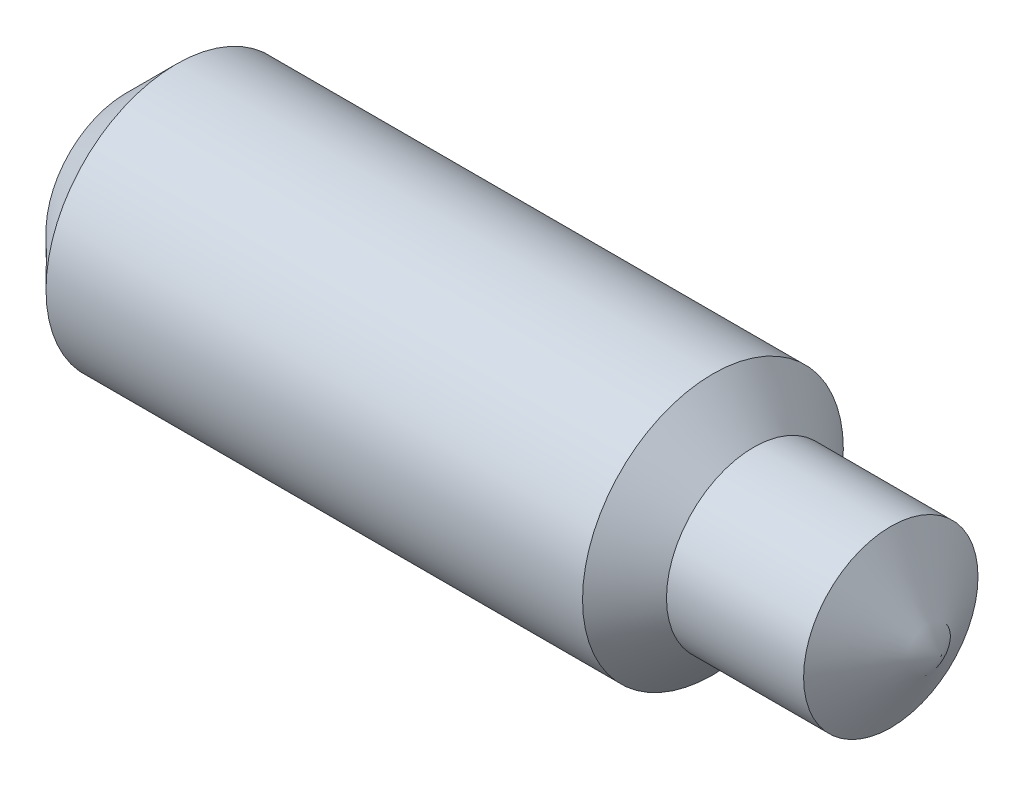
SolidWorks part; units mm, degrees
ref_plane "Front" through (0, 0, 0) normal (0, 0, 1) x (1, 0, 0)
ref_plane "Top" through (0, 0, 0) normal (0, 1, 0) x (1, 0, 0)
ref_plane "Right" through (0, 0, 0) normal (1, 0, 0) x (0, 0, -1)
sketch "Sketch1" plane through (0, 0, 0) normal (0, 0, 1) x (1, 0, 0)
  line L0 (-1.3284, 0) -> (23.5063, 0) construction
  line L1 (0, 0) -> (0, 4)
  line L2 (0, 4) -> (18, 4)
  line L3 (18, 4) -> (19.25, 2.675)
  line L4 (19.25, 2.675) -> (25, 2.675)
  line L5 (25, 0) -> (25, 2.675)
  line L6 (0, 0) -> (25, 0)
revolve "Base" add sketch "Sketch1" angle 360 about L0
cosmetic thread "ThreadCosmetic1" [suppressed] parameters "D1"=18, "D2"=4.917
chamfer "HeadChamfer" distance 1.5415 angle 45 1 edges at (0, 0, 4)
sketch "Sketch2" plane through (0, 0, 0) normal (0, 1, 0) x (1, 0, 0)
  line L0 (27.0527, 0) -> (22.5603, 0) construction
  line L2 (25, 0) -> (23.4556, 2.675)
  line L3 (25, -2.675) -> (25, 2.675) construction
  line L4 (23.4556, 2.675) -> (23.4556, 5)
  line L5 (0, 2.4585) -> (0, -2.4585) construction
  line L6 (-1.3284, 0) -> (23.5063, 0) construction
  line L8 (25, 2.675) -> (19.25, 2.675) construction
  line L9 (23.4556, 5) -> (27, 5)
  line L10 (27, 5) -> (27, 0)
  line L11 (27, 0) -> (25, 0)
  dimension "D1" = 60
  dimension "D3" = 10
  dimension "D2" = 27
revolve "Cut-Extrude3" cut sketch "Sketch2" angle 360 about L0
chamfer "Chamfer2" [suppressed] distance 1.5415 angle 45
sketch "Sketch3" plane through (0, 0, 0) normal (0, 0, 1) x (1, 0, 0)
  line L0 (0.7708, 4) -> (1.5415, 2.665)
  line L1 (1.5415, 2.665) -> (2.3123, 4)
  line L2 (2.3123, 4) -> (2.3123, 4.5)
  line L3 (2.3123, 4.5) -> (0.7708, 4.5)
  line L4 (0.7708, 4.5) -> (0.7708, 4)
  line L5 (0, 0) -> (10.4821, 0) construction
  line L7 (1.5415, 4) -> (1.5415, -4) construction
  dimension "D1" = 60
  dimension "D2" = 60
  dimension "D3" = 0.5
  dimension "D4" = 8
  dimension "D5" = 1.5415
revolve "Cut-Revolve10" [suppressed] cut sketch "Sketch3" angle 360 about L5
pattern_linear "LPattern10" [suppressed] count 10 spacing 1.8498 along (1, 0, 0) of bodies 103
equation "\"D1@HeadChamfer\" =  (\"d@Sketch1\" - \"D2@ThreadCosmetic1\" ) / 2 "
equation "\"D1@Chamfer2\" = \"D1@HeadChamfer\""
equation "\"D2@Sketch2\" = \"l@Sketch1\" + 2"
equation "\"D3@Sketch2\" = \"d@Sketch1\" + 2"
equation "\"D4@Sketch3\" = \"d@Sketch1\""
equation "\"D5@Sketch3\" =  ( \"d@Sketch1\" - \"D2@ThreadCosmetic1\" )  / 2"
equation "\"D3@LPattern10\" = \"D5@Sketch3\" * 1.2"
equation "\"D1@LPattern10\" = \"b@Sketch1\" / \"D3@LPattern10\""
